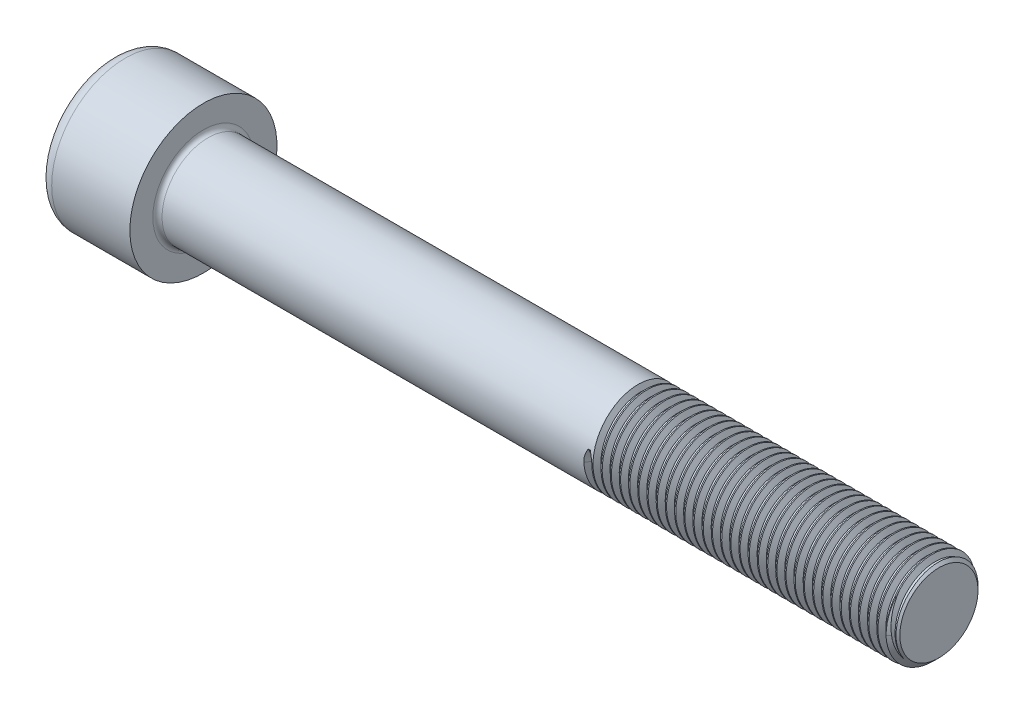
SolidWorks part; units mm, degrees
ref_plane "Front Plane" through (0, 0, 0) normal (0, 0, 1) x (1, 0, 0)
ref_plane "Top Plane" through (0, 0, 0) normal (0, 1, 0) x (1, 0, 0)
ref_plane "Right Plane" through (0, 0, 0) normal (1, 0, 0) x (0, 0, -1)
sketch "Sketch1" plane through (0, 0, 0) normal (0, 0, 1) x (1, 0, 0)
  line L0 (0, 4) -> (0, 6.5)
  line L1 (1.5, 8) -> (10, 8)
  line L2 (10, 8) -> (10, 5.5)
  line L3 (10.5, 5) -> (89.25, 5)
  line L4 (90, 4.25) -> (90, 0)
  line L5 (90, 0) -> (7.3094, 0)
  line L6 (7.3094, 0) -> (5, 4)
  line L7 (5, 4) -> (0, 4)
  line L8 (0, 0) -> (6.5931, 0) construction
  line L9 (0, 0) -> (0, 2.8611) construction
  line L10 (89.25, 5) -> (90, 4.25)
  arc A0 (10, 5.5) -> (10.5, 5) centre (10.5, 5.5) ccw
  arc A1 (0, 6.5) -> (1.5, 8) centre (1.5, 6.5) cw
  point P6 (90, 5)
  point P14 (10, 5)
  point P17 (0, 8)
  point P20 (0, 0)
  dimension "D8" = 0.5
  dimension "D9" = 1.5
  dimension "D1" = 8
  dimension "D2" = 5
  dimension "D3" = 5
  dimension "D4" = 4
  dimension "D5" = 60
  dimension "D6" = 10
  dimension "D7" = 80
revolve "Revolve1" add sketch "Sketch1" angle 360 about L8
sketch "Sketch2" plane through (0, 0, 0) normal (-1, 0, 0) x (0, 0, 1)
  line L1 (-4.6188, 0) -> (-2.3094, -4)
  line L2 (-2.3094, -4) -> (2.3094, -4)
  line L3 (2.3094, -4) -> (4.6188, 0)
  line L4 (4.6188, 0) -> (2.3094, 4)
  line L5 (2.3094, 4) -> (-2.3094, 4)
  line L6 (-2.3094, 4) -> (-4.6188, 0)
  circle A0 centre (0, 0) radius 4 construction
  circle A1 centre (0, 0) radius 4 construction
  circle M7 centre (0, 0) radius 4
extrude "Cut-Extrude2" cut sketch "Sketch2" against normal up to vertex (5 mm away) contours L6 L1 M7 | L1 L2 M7 | L2 L3 M7 | L3 L4 M7 | L4 L5 M7 | L5 L6 M7 region at (0, 0, -4.1343) region at (0, -3.5804, -2.0671) region at (0, 3.5804, -2.0671) region at (0, -3.5804, 2.0671) region at (0, 3.5804, 2.0671) region at (0, 0, 4.1343) up to point (5, 4, 0)
thread "Thread1" pitch 1 method cut profile "Thread Profile1" start angle 0, offset 2, length 34, pitch 1, diameter 10
ref_plane "Plane1" through (91.25, 0, 5) normal (0, -1, 0) x (0, 0, 1)
sketch "Thread Profile1" plane through (91.25, 0, 5) normal (0, -1, 0) x (0, 0, 1)
  line L0 (0, 0) -> (0, 1) construction
  line L11 (0, 0) -> (0, 0.875)
  line L12 (0, 0.875) -> (-0.5413, 0.5625)
  line L13 (-0.5413, 0.5625) -> (-0.5413, 0.3125)
  line L15 (-0.5413, 0.3125) -> (0, 0)
  line L17 (-0.5413, 0.4375) -> (0, 0.4375) construction
  point P2 (0, 0)
  dimension "Pitch" = 1
  dimension "Profile_Angle" = 60
  dimension "Profile_Land" = 0.25
  dimension "Profile_Height" = 0.5413
sketch "Sketch5" plane through (0, 0, 0) normal (0, -1, 0) x (1, 0, 0)
  line L0 (57.25, 6.5) -> (56.375, 6.5)
  line L4 (56.9375, 4.4587) -> (57.25, 5)
  line L5 (57.25, 5) -> (56.375, 5)
  line L6 (56.375, 5) -> (56.6875, 4.4587)
  line L7 (56.6875, 4.4587) -> (56.9375, 4.4587)
  line L8 (56.9375, 4.4587) -> (57.25, 5)
  line L9 (57.25, 5) -> (56.375, 5)
  line L10 (56.375, 5) -> (56.6875, 4.4587)
  line L11 (56.6875, 4.4587) -> (56.9375, 4.4587)
  dimension "D1" = 0
  dimension "D2" = 1.5
revolve "Cut-Revolve1" cut sketch "Sketch5" angle 360 about L0 region at (56.8125, 0, 4.7795)
